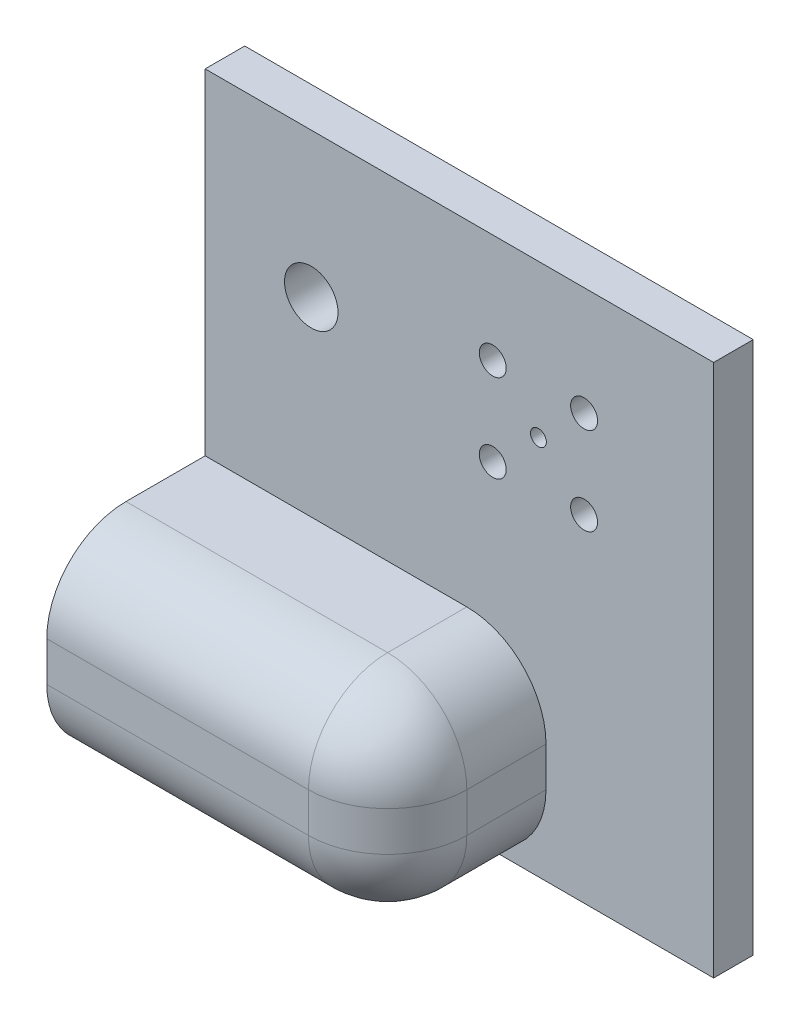
SolidWorks part; units mm, degrees
ref_plane "Front Plane" through (0, 0, 0) normal (0, 0, 1) x (1, 0, 0)
ref_plane "Top Plane" through (0, 0, 0) normal (0, 1, 0) x (1, 0, 0)
ref_plane "Right Plane" through (0, 0, 0) normal (1, 0, 0) x (0, 0, -1)
sketch "Sketch1" plane through (0, 0, 0) normal (0, 0, 1) x (1, 0, 0)
  line L5 (-18.3257, 122) -> (66.6743, 122)
  line L6 (-18.3257, 122) -> (-18.3257, -5)
  line L7 (-18.3257, -5) -> (66.6743, -5)
  line L8 (66.6743, 122) -> (66.6743, -5)
  dimension "D1" = 127
  dimension "D2" = 85
extrude "Boss-Extrude1" add sketch "Sketch1" along normal blind 5
sketch "Sketch2" plane through (0, 0, 0) normal (0, 0, 1) x (1, 0, 0)
  line L1 (17.9899, 89.6207) -> (29.5291, 89.6207)
  line L2 (17.9899, 89.6207) -> (17.9899, 78.537)
  line L3 (17.9899, 78.537) -> (29.5291, 78.537)
  line L4 (29.5291, 89.6207) -> (29.5291, 78.537)
  line L5 (12.9899, 94.6207) -> (34.5291, 94.6207)
  line L6 (12.9899, 94.6207) -> (12.9899, 73.537)
  line L7 (12.9899, 73.537) -> (34.5291, 73.537)
  line L8 (34.5291, 94.6207) -> (34.5291, 73.537)
  circle A0 centre (23.7595, 84.0788) radius 8
  circle A1 centre (17.9899, 89.6207) radius 0.7791
  circle A2 centre (29.5291, 89.6207) radius 0.7326
  circle A3 centre (29.5291, 78.537) radius 0.7634
  circle A4 centre (17.9899, 78.537) radius 0.9336
  dimension "D1" = 16
  dimension "D2" = 16
  dimension "D3" = 8
  dimension "D4" = 8
  dimension "D5" = 5
  dimension "D6" = 5
  dimension "D7" = 5
  dimension "D8" = 5
hole_wizard "CSK for M3 Flat Head Machine Screw1" positions "Sketch3" profile "Sketch4" countersink size "M3" standard "ANSI Metric"
sketch "Sketch3" plane through (0, 0, 0) normal (0, 0, -1) x (-1, 0, 0)
  point P0 (-29.5291, 78.537)
  point P3 (-29.5291, 89.6207)
  point P6 (-17.9899, 89.6207)
  point P9 (-17.9899, 78.537)
sketch "Sketch4" plane through (29.5291, 78.537, 0) normal (1, 0, 0) x (0, 1, 0)
  line L0 (0, 0) -> (0, 11.0215)
  line L1 (0, 11.0215) -> (1.7, 10)
  line L2 (1.7, 10) -> (1.7, 1.45)
  line L3 (1.7, 1.45) -> (3.15, 0)
  line L5 (3.15, 0) -> (0, 0)
  line L6 (-1.7, 1.45) -> (-3.15, 0) construction
  line L10 (0, 11.0215) -> (-1.7, 10) construction
  line L11 (0, -6.35) -> (0, 107.95) construction
  dimension "Hole Dia." = 3.4
  dimension "Hole Depth" = 10
  dimension "Near C'Sink Dia." = 6.3
  dimension "Near C'Sink Angle" = 90
  dimension "Drill Angle" = 118
sketch "Sketch5" plane through (0, 0, 5) normal (0, 0, 1) x (1, 0, 0)
  circle A0 centre (23.7595, 84.0788) radius 1
  dimension "D1" = 2
extrude "Cut-Extrude1" cut sketch "Sketch5" against normal offset from surface (4 mm away) 1 up to face at (26.3791, 78.537, 0)
sketch "Sketch6" plane through (0, 0, 5) normal (0, 0, 1) x (1, 0, 0)
  line L0 (-18.3257, 122) -> (-18.3257, -5) construction
  line L1 (24.7163, 61.037) -> (-18.3257, 61.037)
  line L2 (24.7163, 61.037) -> (24.7163, 36.037)
  line L3 (24.7163, 36.037) -> (-18.3257, 36.037)
  line L4 (-18.3257, 61.037) -> (-18.3257, 36.037)
  circle A0 centre (17.9899, 78.537) radius 1.7 construction
  dimension "D1" = 25
  dimension "D2" = 17.5
extrude "Boss-Extrude2" add sketch "Sketch6" along normal offset from surface (20 mm away) 25 up to face at (26.3791, 78.537, 0)
sketch "Sketch7" plane through (-18.3257, 0, 0) normal (-1, 0, 0) x (0, 0, 1)
  line L0 (25, 61.037) -> (5, 61.037) construction
  line L1 (25, 61.037) -> (25, 36.037) construction
  circle A0 centre (15, 48.537) radius 5.3578
  dimension "D1" = 10.7156
  dimension "D2" = 12.5
  dimension "D3" = 10
hole_wizard "1/4 NPT Tapped Hole1" positions "Sketch8" profile "Sketch9" size "1/4" standard "ANSI Inch"
sketch "Sketch8" plane through (-18.3257, 0, 0) normal (-1, 0, 0) x (0, 0, 1)
  point P0 (15, 48.537)
sketch "Sketch9" plane through (-18.3257, 48.537, 15) normal (0, 1, 0) x (0, 0, 1)
  line L0 (0, 0) -> (0, 20.4123)
  line L1 (5.5626, 17.07) -> (0, 20.4123)
  line L2 (-5.5626, 17.07) -> (0, 20.4123) construction
  line L3 (5.5626, 17.07) -> (5.5626, 10.02)
  line L4 (5.5626, 10.02) -> (6.558, 10.02)
  line L5 (6.558, 10.02) -> (6.858, 0)
  line L6 (-6.558, 10.02) -> (-6.858, 0) construction
  line L7 (6.858, 0) -> (0, 0)
  line L8 (0, -6.35) -> (0, 107.95) construction
  line L11 (-5.5626, 10.02) -> (-6.558, 10.02) construction
  dimension "Tap Drill Dia." = 11.1252
  dimension "Tap Drill Depth" = 17.07
  dimension "Thread Dia." = 13.716
  dimension "Thread Angle" = 3.43
  dimension "Thread Depth" = 10.02
  dimension "Drill Angle" = 118
sketch "Sketch10" plane through (0, 122, 0) normal (0, 1, 0) x (1, 0, 0)
  line L0 (22.7595, -1) -> (24.7595, -1) construction
  line L1 (24.2595, -3) -> (23.2595, -3)
  line L2 (24.2595, -3) -> (24.2595, -1)
  line L3 (24.2595, -1) -> (23.2595, -1)
  line L4 (23.2595, -3) -> (23.2595, -1)
  line L5 (22.7595, -1) -> (24.7595, -1)
  line L6 (24.7595, -1) -> (23.7595, -3)
  line L7 (23.7595, -3) -> (22.7595, -1)
  dimension "D1" = 1
  dimension "D2" = 2
  dimension "D3" = 0
  dimension "D4" = 0.5
  dimension "D5" = 0.5
  dimension "D6" = 0.5
extrude "Cut-Extrude7" cut sketch "Sketch10" along normal up to surface (35.5418 mm away) from vertex contours L7 L6 L2 L3 L4 | L7 L4 L5 | L6 L5 L2 region at (23.7595, 122, 1.7778) region at (24.4262, 122, 1.3333) region at (23.0928, 122, 1.3333) up to face at (24.7595, 84.0788, 1) starting at point (-18.3257, 48.537, 15)
sketch "Sketch13" plane through (-18.3257, 0, 0) normal (-1, 0, 0) x (0, 0, 1)
  line L1 (15.5, 49.037) -> (14.5, 49.037)
  line L2 (15.5, 49.037) -> (15.5, 48.037)
  line L3 (15.5, 48.037) -> (14.5, 48.037)
  line L4 (14.5, 49.037) -> (14.5, 48.037)
  dimension "D1" = 1
  dimension "D2" = 1
  dimension "D3" = 0.5
  dimension "D4" = 0.5
sketch "Sketch14" plane through (0, 0, 1) normal (0, 0, 1) x (1, 0, 0)
  line L0 (23.2595, 83.2128) -> (24.2595, 83.2128)
sketch "Sketch17" plane through (0, 0, 5) normal (0, 0, 1) x (1, 0, 0)
  line L0 (24.2595, 83.2128) -> (23.2595, 83.2128)
sketch "Sketch18" plane through (23.2595, 0, 0) normal (1, 0, 0) x (0, 0, -1)
  line L0 (-1, 83.2128) -> (-5, 83.2128)
sketch "Sketch16" plane through (0, -5, 0) normal (0, -1, 0) x (-1, 0, 0)
  line L0 (-23.2595, -1) -> (-24.2595, -1) construction
  line L1 (-23.2595, -1) -> (-25.2595, -1)
  line L2 (-23.2595, -1) -> (-23.2595, -3)
  line L3 (-23.2595, -3) -> (-25.2595, -3)
  line L4 (-25.2595, -1) -> (-25.2595, -3)
  line L5 (-23.2595, -1) -> (-23.2595, -5) construction
  line L6 (-2.0866, -16) -> (-2.0866, -14)
  line L7 (-2.0866, -14) -> (-23.2595, -1)
  line L8 (-23.2595, -3) -> (-2.0866, -16)
  line L10 (-2.0866, -16) -> (-0.0866, -16)
  line L11 (-2.0866, -16) -> (-2.0866, -14)
  line L12 (-2.0866, -14) -> (-0.0866, -14)
  line L13 (-0.0866, -16) -> (-0.0866, -14)
  line M5 (-66.6743, -5) -> (18.3257, -5)
  dimension "D1" = 0
  dimension "D2" = 2
  dimension "D3" = 2
  dimension "D4" = 0
  dimension "D5" = 1
  dimension "D6" = 1
  dimension "D7" = 2
  dimension "D8" = 2
extrude "Cut-Extrude8" cut sketch "Sketch16" against normal mid plane 3 from vertex contours L1 L4 L3 L2 | L2 L8 L7 M5 | L8 L6 L7 M5 | L10 L13 L12 L6 region at (24.2595, -5, 2) region at (20.726, -5, 3.4444) region at (10.2572, -5, 10.0167) region at (1.0866, -5, 15) starting at point (2.0866, 48.537, 15)
fillet "Fillet1" radius 10 2 edges at (3.1953, 61.037, 25) (3.1953, 36.037, 25)
fillet "Fillet2" radius 10 5 edges at (24.7163, 58.1081, 22.0711) (24.7163, 61.037, 10) (24.7163, 36.037, 10) (24.7163, 38.9659, 22.0711) (24.7163, 48.537, 25) first distance on face at (3.1953, 57.0725, 21.0355) first distance on face at (3.1953, 61.037, 10) first distance on face at (3.1953, 36.037, 10) first distance on face at (3.1953, 40.0015, 21.0355) first distance on face at (3.1953, 48.537, 25)
sketch "Sketch19" plane through (0, 0, 5) normal (0, 0, 1) x (1, 0, 0)
  line L1 (71.216, 132.4335) -> (-24.0983, 132.4335)
  line L2 (71.216, 132.4335) -> (71.216, -15.5933)
  line L3 (71.216, -15.5933) -> (-24.0983, -15.5933)
  line L4 (-24.0983, 132.4335) -> (-24.0983, -15.5933)
  line L5 (45.886, 103.3534) -> (-18.3257, 103.3534)
  line L6 (45.886, 103.3534) -> (45.886, 36.037)
  line L7 (45.886, 36.037) -> (-18.3257, 36.037)
  line L8 (-18.3257, 103.3534) -> (-18.3257, 36.037)
extrude "Cut-Extrude9" cut sketch "Sketch19" against normal through all
chamfer "Chamfer3" distance 1.4 angle 50 1 edges at (12.6731, 50.037, 9.5) first distance on face at (12.6731, 48.537, 9.5)
chamfer "Chamfer4" distance 1.2 angle 50 1 edges at (12.6731, 47.037, 9.5) first distance on face at (12.6731, 47.837, 9.5)
sketch "Sketch20" plane through (0, 0, 5) normal (0, 0, 1) x (1, 0, 0)
  circle A0 centre (-4.9247, 85.093) radius 1.9874
hole_wizard "1/4 Clearance Hole1" positions "Sketch21" profile "Sketch22" hole size "1/4" standard "ANSI Inch" end condition through all
sketch "Sketch21" plane through (0, 0, 5) normal (0, 0, 1) x (1, 0, 0)
  point P0 (-4.9247, 85.093)
sketch "Sketch22" plane through (-4.9247, 85.093, 5) normal (1, 0, 0) x (0, -1, 0)
  line L0 (0, 0) -> (0, 5)
  line L1 (0, 5) -> (3.3782, 5)
  line L2 (3.3782, 5) -> (3.3782, 0)
  line L5 (3.3782, 0) -> (0, 0)
  line L11 (0, -6.35) -> (0, 107.95) construction
  dimension "Thru Hole Dia." = 6.7564
  dimension "Thru Hole Depth" = 5
equation "\"D1@Sketch7\"=25.4*27/64"
